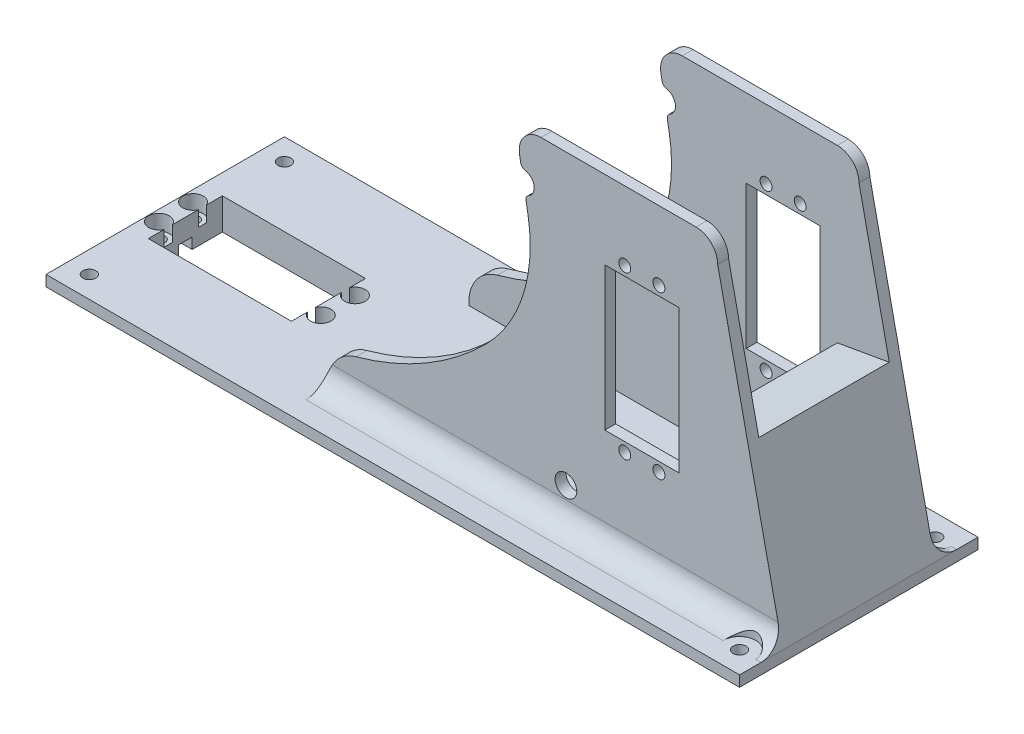
SolidWorks part; units mm, degrees
ref_plane "Front Plane" through (0, 0, 0) normal (0, 0, 1) x (1, 0, 0)
ref_plane "Top Plane" through (0, 0, 0) normal (0, 1, 0) x (1, 0, 0)
ref_plane "Right Plane" through (0, 0, 0) normal (1, 0, 0) x (0, 0, -1)
sketch "Sketch1" plane through (0, 0, 0) normal (0, 0, 1) x (1, 0, 0)
  line L7 (146.05, 3.175) -> (146.05, 4.063)
  line L8 (0, 0) -> (279.4, 0)
  line L9 (0, 0) -> (0, 3.175)
  line L10 (0, 3.175) -> (279.4, 3.175)
  line L11 (279.4, 0) -> (279.4, 3.175)
  line L12 (260.35, 3.175) -> (215.9, 3.175)
  line L13 (260.35, 3.175) -> (260.35, 91.44) construction
  line L14 (254, 97.79) -> (222.25, 97.79)
  line L15 (215.9, 3.175) -> (215.9, 91.44) construction
  line L16 (260.35, 91.44) -> (279.4, 3.175)
  line L17 (165.0718, 64.0362) -> (215.9, 13.208) construction
  line L18 (170.5184, 69.8101) -> (222.7846, 20.5062)
  line L19 (215.9, 91.44) -> (215.9, 89.5783)
  line L20 (0, 19.05) -> (0, 30.1625)
  line L21 (3.175, 19.05) -> (3.175, 30.1625)
  line L22 (3.175, 30.1625) -> (0, 30.1625) construction
  line L23 (26.8735, 12.7) -> (70.8676, 19.05)
  line L24 (238.125, 97.79) -> (238.125, 3.175) construction
  line L25 (165.0718, 64.0362) -> (292.0718, 64.0362) construction
  line L26 (238.125, 76.7362) -> (292.0718, 67.2112)
  line L27 (238.125, 51.3362) -> (292.0718, 60.8612)
  line L28 (215.9, 13.208) -> (203.4178, 83.998) construction
  arc A6 (260.35, 91.44) -> (254, 97.79) centre (254, 91.44) ccw
  arc A7 (222.25, 97.79) -> (215.9, 91.44) centre (222.25, 91.44) ccw
  circle A9 centre (215.9, 13.208) radius 3.175
  arc A10 (216.7962, 82.0441) -> (216.9572, 88.0838) centre (215.9, 85.09) ccw
  arc A11 (154.4343, 15.0798) -> (215.6899, 80.8367) centre (131.5684, 97.79) ccw
  arc A12 (146.05, 4.063) -> (154.4343, 15.0798) centre (157.48, 4.063) cw
  circle A13 centre (215.9, 13.208) radius 10.033
  circle A14 centre (165.0718, 64.0362) radius 3.175
  circle A15 centre (165.0718, 64.0362) radius 7.9375
  arc A16 (0, 19.05) -> (15.875, 3.175) centre (15.875, 19.05) ccw
  arc A17 (3.175, 19.05) -> (26.8735, 12.7) centre (15.875, 19.05) ccw
  circle A18 centre (15.875, 19.05) radius 15.875 construction
  circle A19 centre (15.875, 19.05) radius 12.7 construction
  arc A20 (70.8676, 19.05) -> (158.9067, 69.0358) centre (51.0253, 156.5215) ccw
  arc A21 (215.6899, 80.8367) -> (216.7962, 82.0441) centre (217.2436, 80.5236) cw
  arc A22 (215.9, 89.5783) -> (216.9572, 88.0838) centre (217.485, 89.5783) ccw
  arc A23 (3.175, 30.1625) -> (0, 30.1625) centre (1.5875, 30.1625) ccw
  circle A24 centre (238.125, 64.0362) radius 12.7
  circle A25 centre (292.0718, 64.0362) radius 3.175
  circle A26 centre (203.4178, 83.998) radius 3.175
  point P11 (260.35, 97.79)
  point P14 (215.9, 97.79)
  point P27 (146.05, 13.208)
  point P48 (215.9, 81.915)
  point P51 (215.9, 88.265)
  dimension "D4" = 97.79
  dimension "D6" = 6.35
  dimension "D8" = 6.35
  dimension "D7" = 6.35
  dimension "D10" = 12.7
  dimension "D12" = 11.43
  dimension "D13" = 6.35
  dimension "D16" = 15.875
  dimension "D18" = 31.75
  dimension "D24" = 1.585
  dimension "D26" = 25.4
  dimension "D27" = 6.35
  dimension "D1" = 3.175
  dimension "D2" = 279.4
  dimension "D3" = 44.45
  dimension "D5" = 19.05
  dimension "D9" = 71.882
  dimension "D11" = 114.3
  dimension "D14" = 71.882
  dimension "D15" = 45
  dimension "D17" = 200.025
  dimension "D19" = 30.1625
  dimension "D21" = 12.7
  dimension "D22" = 44.45
  dimension "D23" = 19.05
  dimension "D25" = 127
  dimension "D28" = 35
  dimension "D20" = 3.175
ref_plane "Plane2" through (0, 0, 17.526) normal (0, 0, 1) x (1, 0, 0)
ref_plane "Plane3" through (0, 0, 34.925) normal (0, 0, 1) x (1, 0, 0)
ref_plane "Plane4" through (0, 0, 22.2885) normal (0, 0, 1) x (1, 0, 0)
sketch "Sketch4" plane through (0, 0, 22.2885) normal (0, 0, 1) x (1, 0, 0)
  line L0 (215.9, 91.44) -> (215.9, 89.5783) construction
  line L1 (254, 97.79) -> (222.25, 97.79) construction
  line L2 (260.35, 91.44) -> (279.4, 3.175) construction
  line L3 (0, 3.175) -> (279.4, 3.175) construction
  line L4 (146.05, 3.175) -> (146.05, 4.063) construction
  line L5 (215.9, 91.44) -> (215.9, 89.5783)
  line L6 (254, 97.79) -> (222.25, 97.79)
  line L7 (260.35, 91.44) -> (279.4, 3.175)
  line L8 (0, 3.175) -> (279.4, 3.175)
  line L9 (146.05, 3.175) -> (146.05, 4.063)
  arc A0 (154.4343, 15.0798) -> (215.6899, 80.8367) centre (131.5684, 97.79) ccw construction
  arc A1 (216.7962, 82.0441) -> (215.6899, 80.8367) centre (217.2436, 80.5236) ccw construction
  arc A2 (216.7962, 82.0441) -> (216.9572, 88.0838) centre (215.9, 85.09) ccw construction
  arc A3 (215.9, 89.5783) -> (216.9572, 88.0838) centre (217.485, 89.5783) ccw construction
  arc A4 (222.25, 97.79) -> (215.9, 91.44) centre (222.25, 91.44) ccw construction
  arc A5 (260.35, 91.44) -> (254, 97.79) centre (254, 91.44) ccw construction
  arc A6 (154.4343, 15.0798) -> (146.05, 4.063) centre (157.48, 4.063) ccw construction
  arc A7 (154.4343, 15.0798) -> (215.6899, 80.8367) centre (131.5684, 97.79) ccw
  arc A8 (216.7962, 82.0441) -> (215.6899, 80.8367) centre (217.2436, 80.5236) ccw
  arc A9 (216.7962, 82.0441) -> (216.9572, 88.0838) centre (215.9, 85.09) ccw
  arc A10 (215.9, 89.5783) -> (216.9572, 88.0838) centre (217.485, 89.5783) ccw
  arc A11 (222.25, 97.79) -> (215.9, 91.44) centre (222.25, 91.44) ccw
  arc A12 (260.35, 91.44) -> (254, 97.79) centre (254, 91.44) ccw
  arc A13 (154.4343, 15.0798) -> (146.05, 4.063) centre (157.48, 4.063) ccw
  circle A14 centre (215.9, 13.208) radius 3.175 construction
  circle A15 centre (215.9, 13.208) radius 3.175
extrude "Boss-Extrude1" add sketch "Sketch4" against normal blind 3.175 contours A7 A13 L9 L8 L7 A12 L6 A11 L5 A10 A9 A8 region at (228.3614, 40.3693, 22.2885)
sketch "Sketch5" plane through (0, 0, 34.925) normal (0, 0, 1) x (1, 0, 0)
  line L0 (279.4, 0) -> (279.4, 3.175) construction
  line L1 (0, 3.175) -> (279.4, 3.175) construction
  line L2 (0, 0) -> (0, 3.175) construction
  line L3 (0, 0) -> (279.4, 0) construction
  line L4 (279.4, 0) -> (279.4, 3.175)
  line L5 (0, 3.175) -> (279.4, 3.175)
  line L6 (0, 0) -> (0, 3.175)
  line L7 (0, 0) -> (279.4, 0)
  line L8 (146.05, 3.175) -> (146.05, 4.063) construction
  line L9 (146.05, 3.175) -> (146.05, 4.063)
  line L10 (76.2, 0) -> (76.2, 3.175)
  dimension "D1" = 69.85
extrude "Boss-Extrude2" add sketch "Sketch5" against normal up to surface (34.925 mm away) contours L5 L7 L4 region at (177.8, 1.5875, 34.925) up to plane "Front Plane"
sketch "Sketch6" plane through (0, 0, 19.1135) normal (0, 0, -1) x (-1, 0, 0)
  line L0 (-254, 97.79) -> (-254, 3.175)
  line L1 (-238.125, 51.3362) -> (-292.0718, 60.8612) construction
  line L2 (-238.125, 51.3362) -> (-292.0718, 60.8612)
  line L3 (-239.2291, 45.083) -> (-293.1758, 54.608)
  line L5 (-215.9, 89.5783) -> (-215.9, 91.44)
  line L6 (-222.25, 97.79) -> (-254, 97.79)
  line L7 (-260.35, 91.44) -> (-279.4, 3.175)
  line L8 (-279.4, 3.175) -> (-146.05, 3.175)
  line L9 (-146.05, 3.175) -> (-146.05, 4.063)
  line L10 (-215.9, 89.5783) -> (-215.9, 91.44)
  line L11 (-222.25, 97.79) -> (-254, 97.79)
  line L12 (-260.35, 91.44) -> (-279.4, 3.175)
  line L13 (-279.4, 3.175) -> (-146.05, 3.175)
  line L14 (-146.05, 3.175) -> (-146.05, 4.063)
  arc A7 (-215.6899, 80.8367) -> (-154.4343, 15.0798) centre (-131.5684, 97.79) ccw
  arc A8 (-215.6899, 80.8367) -> (-216.7962, 82.0441) centre (-217.2436, 80.5236) ccw
  arc A9 (-216.9572, 88.0838) -> (-216.7962, 82.0441) centre (-215.9, 85.09) ccw
  arc A10 (-216.9572, 88.0838) -> (-215.9, 89.5783) centre (-217.485, 89.5783) ccw
  arc A11 (-215.9, 91.44) -> (-222.25, 97.79) centre (-222.25, 91.44) ccw
  arc A12 (-254, 97.79) -> (-260.35, 91.44) centre (-254, 91.44) ccw
  arc A13 (-146.05, 4.063) -> (-154.4343, 15.0798) centre (-157.48, 4.063) ccw
  arc A14 (-215.6899, 80.8367) -> (-154.4343, 15.0798) centre (-131.5684, 97.79) ccw
  arc A15 (-215.6899, 80.8367) -> (-216.7962, 82.0441) centre (-217.2436, 80.5236) ccw
  arc A16 (-216.9572, 88.0838) -> (-216.7962, 82.0441) centre (-215.9, 85.09) ccw
  arc A17 (-216.9572, 88.0838) -> (-215.9, 89.5783) centre (-217.485, 89.5783) ccw
  arc A18 (-215.9, 91.44) -> (-222.25, 97.79) centre (-222.25, 91.44) ccw
  arc A19 (-254, 97.79) -> (-260.35, 91.44) centre (-254, 91.44) ccw
  arc A20 (-146.05, 4.063) -> (-154.4343, 15.0798) centre (-157.48, 4.063) ccw
  line M22 (-260.35, 91.44) -> (-279.4, 3.175)
  line M23 (-279.4, 3.175) -> (-146.05, 3.175)
  dimension "D1" = 0
  dimension "D2" = 6.35
extrude "Boss-Extrude4" add sketch "Sketch6" along normal up to surface (19.1135 mm away) contours L0 L3 M22 M23 region at (264.4814, 24.2651, 19.1135) up to plane "Front Plane"
mirror "Mirror4" about plane through (0, 0, 0) normal (0, 0, 1) of "Boss-Extrude4", "Boss-Extrude2", "Boss-Extrude1"
sketch "Sketch7" plane through (0, 0, 22.2885) normal (0, 0, 1) x (1, 0, 0)
  circle A0 centre (238.125, 64.0362) radius 3.175
  point P0 (238.125, 64.0362)
  dimension "D1" = 6.35
extrude "Cut-Extrude1" [suppressed] cut sketch "Sketch7" against normal through all
sketch "Sketch8" plane through (0, 0, -22.2885) normal (0, 0, -1) x (-1, 0, 0)
  line L0 (-215.9, 13.208) -> (-203.4178, 83.998) construction
  line L1 (-207.8996, 58.5805) -> (-204.1972, 79.5778)
  line L2 (-202.6384, 88.4181) -> (-202.3, 90.3373)
  line L3 (-222.25, 97.79) -> (-208.5535, 97.79)
  line L4 (-215.9, 89.5783) -> (-215.9, 91.44)
  line L5 (-222.25, 97.79) -> (-254, 97.79)
  line L6 (-260.35, 91.44) -> (-279.4, 3.175)
  line L7 (-279.4, 3.175) -> (-146.05, 3.175)
  line L8 (-215.9, 89.5783) -> (-215.9, 91.44)
  line L15 (-279.4, 3.175) -> (-146.05, 3.175)
  line L18 (-146.05, 3.175) -> (-146.05, 4.063)
  line L19 (-146.05, 3.175) -> (-146.05, 4.063)
  circle A0 centre (-203.4178, 83.998) radius 3.175 construction
  arc A1 (-203.9391, 87.1299) -> (-204.9788, 81.2332) centre (-203.4178, 83.998) ccw
  arc A2 (-204.9788, 81.2332) -> (-204.1972, 79.5778) centre (-205.7581, 79.853) cw
  arc A3 (-203.9391, 87.1299) -> (-202.6384, 88.4181) centre (-204.1993, 88.6933) ccw
  arc A4 (-208.5535, 97.79) -> (-202.3, 90.3373) centre (-208.5535, 91.44) cw
  arc A9 (-146.05, 4.063) -> (-154.4343, 15.0798) centre (-157.48, 4.063) ccw
  arc A10 (-215.6899, 80.8367) -> (-154.4343, 15.0798) centre (-131.5684, 97.79) ccw
  arc A11 (-215.6899, 80.8367) -> (-216.7962, 82.0441) centre (-217.2436, 80.5236) ccw
  arc A12 (-216.9572, 88.0838) -> (-216.7962, 82.0441) centre (-215.9, 85.09) ccw
  arc A13 (-216.9572, 88.0838) -> (-215.9, 89.5783) centre (-217.485, 89.5783) ccw
  arc A14 (-215.9, 91.44) -> (-222.25, 97.79) centre (-222.25, 91.44) ccw
  arc A15 (-254, 97.79) -> (-260.35, 91.44) centre (-254, 91.44) ccw
  arc A17 (-215.6899, 80.8367) -> (-207.8996, 58.5805) centre (-131.5684, 97.79) ccw
  arc A18 (-215.6899, 80.8367) -> (-216.7962, 82.0441) centre (-217.2436, 80.5236) ccw
  arc A19 (-216.9572, 88.0838) -> (-216.7962, 82.0441) centre (-215.9, 85.09) ccw
  arc A20 (-216.9572, 88.0838) -> (-215.9, 89.5783) centre (-217.485, 89.5783) ccw
  arc A21 (-215.9, 91.44) -> (-222.25, 97.79) centre (-222.25, 91.44) ccw
  arc M22 (-154.4343, 15.0798) -> (-215.6899, 80.8367) centre (-131.5684, 97.79) cw
  arc M23 (-215.6899, 80.8367) -> (-216.7962, 82.0441) centre (-217.2436, 80.5236) ccw
  arc M24 (-216.7962, 82.0441) -> (-216.9572, 88.0838) centre (-215.9, 85.09) cw
  arc M25 (-216.9572, 88.0838) -> (-215.9, 89.5783) centre (-217.485, 89.5783) ccw
  line M26 (-215.9, 89.5783) -> (-215.9, 91.44)
  arc M27 (-215.9, 91.44) -> (-222.25, 97.79) centre (-222.25, 91.44) ccw
  dimension "D2" = 1.585
  dimension "D3" = 6.35
  dimension "D1" = 0
extrude "Boss-Extrude5" add sketch "Sketch8" against normal blind 3.175 contours A4 L3 L1 A2 A1 A3 L2 M27 M26 M25 M24 M23 M22 region at (210.2397, 83.1343, -22.2885)
mirror "Mirror5" about plane through (0, 0, 0) normal (0, 0, 1) of "Boss-Extrude5"
fillet "Fillet2" radius 44.45 2 edges at (207.8996, 58.5805, 20.701) (207.8996, 58.5805, -20.701)
sketch "Sketch9" plane through (0, 0, -22.2885) normal (0, 0, -1) x (-1, 0, 0)
  line L0 (-243.125, 77.5812) -> (-233.125, 30.1512) construction
  line L1 (-248.975, 32.8962) -> (-227.275, 32.8962)
  line L2 (-248.975, 32.8962) -> (-248.975, 74.8362)
  line L3 (-248.975, 74.8362) -> (-227.275, 74.8362)
  line L4 (-227.275, 32.8962) -> (-227.275, 74.8362)
  line L5 (-248.975, 32.8962) -> (-227.275, 74.8362) construction
  line L6 (-248.975, 74.8362) -> (-227.275, 32.8962) construction
  circle A0 centre (-243.125, 77.5812) radius 1.75
  circle A1 centre (-233.125, 77.5812) radius 1.75
  circle A2 centre (-243.125, 30.1512) radius 1.75
  circle A3 centre (-233.125, 30.1512) radius 1.75
  point P0 (-238.125, 64.0362)
  point P2 (-238.125, 53.8662)
  point P15 (-238.125, 53.8662)
  dimension "D1" = 3.5
  dimension "D2" = 21.7
  dimension "D3" = 41.94
  dimension "D4" = 47.43
  dimension "D5" = 10
  dimension "D6" = 13.545
extrude "Cut-Extrude2" cut sketch "Sketch9" against normal through all
sketch "Sketch10" plane through (0, 0, 0) normal (0, -1, 0) x (1, 0, 0)
  line L0 (79.355, -5) -> (126.785, 5) construction
  line L1 (124.04, -10.85) -> (82.1, -10.85)
  line L2 (124.04, -10.85) -> (124.04, 10.85)
  line L3 (124.04, 10.85) -> (82.1, 10.85)
  line L4 (82.1, -10.85) -> (82.1, 10.85)
  line L5 (124.04, -10.85) -> (82.1, 10.85) construction
  line L6 (124.04, 10.85) -> (82.1, -10.85) construction
  line L7 (76.2, -34.925) -> (76.2, 34.925) construction
  line L10 (212.725, -22.2885) -> (219.075, -22.2885) construction
  line L11 (212.725, -22.2885) -> (219.075, -22.2885) construction
  circle A0 centre (79.355, -5) radius 1.75
  circle A1 centre (79.355, 5) radius 1.75
  circle A2 centre (126.785, -5) radius 1.75
  circle A3 centre (126.785, 5) radius 1.75
  point P0 (103.07, 0)
  point P13 (103.07, 0)
  point P16 (76.2, 0)
  point P17 (92.9, 0)
  point P20 (82.1, 0)
  point P23 (215.9, -22.2885)
  dimension "D1" = 3.5
  dimension "D2" = 21.7
  dimension "D3" = 41.94
  dimension "D4" = 10
  dimension "D5" = 47.43
  dimension "D6" = 10.8
  dimension "D7" = 123
extrude "Cut-Extrude3" cut sketch "Sketch10" against normal through all
ref_plane "Plane5" through (279.4, 3.175, -34.925) normal (0, 0, -1) x (-1, 0, 0)
sketch "Sketch12" plane through (0, 0, 0) normal (0, -1, 0) x (1, 0, 0)
  line L0 (124.04, 10.85) -> (82.1, 10.85) construction
  line L1 (82.1, 10.85) -> (82.1, -10.85) construction
  line L2 (82.1, -10.85) -> (124.04, -10.85) construction
  line L3 (124.04, -10.85) -> (124.04, 10.85) construction
  line L4 (124.04, 10.85) -> (82.1, 10.85)
  line L5 (82.1, 10.85) -> (82.1, -10.85)
  line L6 (82.1, -10.85) -> (124.04, -10.85)
  line L7 (124.04, -10.85) -> (124.04, 10.85)
  line L9 (129.94, 19.05) -> (76.2, 19.05)
  line L10 (129.94, 19.05) -> (129.94, -19.05)
  line L11 (129.94, -19.05) -> (76.2, -19.05)
  line L12 (76.2, 19.05) -> (76.2, -19.05)
  line L13 (129.94, 19.05) -> (76.2, -19.05) construction
  line L14 (129.94, -19.05) -> (76.2, 19.05) construction
  line L16 (76.2, -34.925) -> (76.2, 34.925) construction
  circle A0 centre (79.355, -5) radius 1.75 construction
  circle A1 centre (79.355, 5) radius 1.75 construction
  circle A2 centre (126.785, 5) radius 1.75 construction
  circle A3 centre (126.785, -5) radius 1.75 construction
  circle A4 centre (79.355, -5) radius 1.75
  circle A5 centre (79.355, 5) radius 1.75
  circle A6 centre (126.785, 5) radius 1.75
  circle A7 centre (126.785, -5) radius 1.75
  point P16 (103.07, 0)
  point P22 (103.07, -10.85)
  point P24 (82.1, 0)
  dimension "D2" = 38.1
extrude "Boss-Extrude6" add sketch "Sketch12" along normal blind 6.02
sketch "Sketch13" plane through (0, 3.175, 0) normal (0, 1, 0) x (1, 0, 0)
  circle A0 centre (126.785, -5) radius 3
  circle A1 centre (126.785, 5) radius 3
  circle A2 centre (79.355, -5) radius 3
  circle A3 centre (79.355, 5) radius 3
  dimension "D1" = 6
extrude "Cut-Extrude4" cut sketch "Sketch13" against normal blind 4.5
sketch "Sketch14" plane through (0, 3.175, 0) normal (0, 1, 0) x (1, 0, 0)
  line L0 (279.4, 34.925) -> (279.4, -34.925) construction
  line L1 (273.05, -28.575) -> (82.55, -28.575)
  line L2 (273.05, -28.575) -> (273.05, 28.575)
  line L3 (273.05, 28.575) -> (82.55, 28.575)
  line L4 (82.55, -28.575) -> (82.55, 28.575)
  line L5 (76.2, -34.925) -> (279.4, -34.925) construction
  point P4 (273.05, 0)
  point P7 (279.4, 0)
  point P8 (177.8, -28.575)
  point P11 (177.8, -34.925)
  dimension "D1" = 190.5
  dimension "D2" = 57.15
hole_wizard "#6 Clearance Hole1" positions "Sketch15" profile "Sketch16" hole size "#6" standard "ANSI Inch" end condition through all
sketch "Sketch15" plane through (0, 3.175, 0) normal (0, 1, 0) x (1, 0, 0)
  point P0 (273.05, -28.575)
  point P3 (273.05, 28.575)
  point P6 (82.55, -28.575)
  point P9 (82.55, 28.575)
sketch "Sketch16" plane through (273.05, 3.175, 28.575) normal (1, 0, 0) x (0, 0, 1)
  line L0 (0, 0) -> (0, 9.195)
  line L1 (0, 9.195) -> (1.8986, 9.195)
  line L2 (1.8986, 9.195) -> (1.8986, 0)
  line L5 (1.8986, 0) -> (0, 0)
  line L11 (0, -6.35) -> (0, 107.95) construction
  dimension "Thru Hole Dia." = 3.7973
  dimension "Thru Hole Depth" = 9.195
fillet "Fillet3" radius 6.35 2 edges at (212.725, 3.175, 22.2885) (212.725, 3.175, -22.2885)
sketch "Sketch17" plane through (0, 3.175, 0) normal (0, 1, 0) x (1, 0, 0)
  circle A0 centre (273.05, -28.575) radius 4.7625
  circle A1 centre (273.05, 28.575) radius 4.7625
  dimension "D1" = 9.525
extrude "Cut-Extrude5" cut sketch "Sketch17" along normal through all
sketch "Sketch18" plane through (0, -6.02, 0) normal (0, -1, 0) x (1, 0, 0)
  line L0 (82.1, 10.85) -> (82.1, -10.85) construction
  line L1 (76.2, -2) -> (82.1, -2)
  line L2 (76.2, -2) -> (76.2, 2)
  line L3 (76.2, 2) -> (82.1, 2)
  line L4 (82.1, -2) -> (82.1, 2)
  line L5 (76.2, -2) -> (82.1, 2) construction
  line L6 (76.2, 2) -> (82.1, -2) construction
  line L7 (129.94, -19.05) -> (129.94, 19.05) construction
  line L8 (124.04, -2) -> (129.94, -2)
  line L9 (124.04, -2) -> (124.04, 2)
  line L10 (124.04, 2) -> (129.94, 2)
  line L11 (129.94, -2) -> (129.94, 2)
  line L12 (124.04, -2) -> (129.94, 2) construction
  line L13 (124.04, 2) -> (129.94, -2) construction
  line L14 (76.2, 19.05) -> (76.2, -19.05) construction
  line L15 (124.04, -10.85) -> (124.04, 10.85) construction
  point P0 (79.15, 0)
  point P7 (126.99, 0)
  point P16 (76.2, 0)
  dimension "D1" = 4
extrude "Cut-Extrude6" cut sketch "Sketch18" against normal blind 3.175
